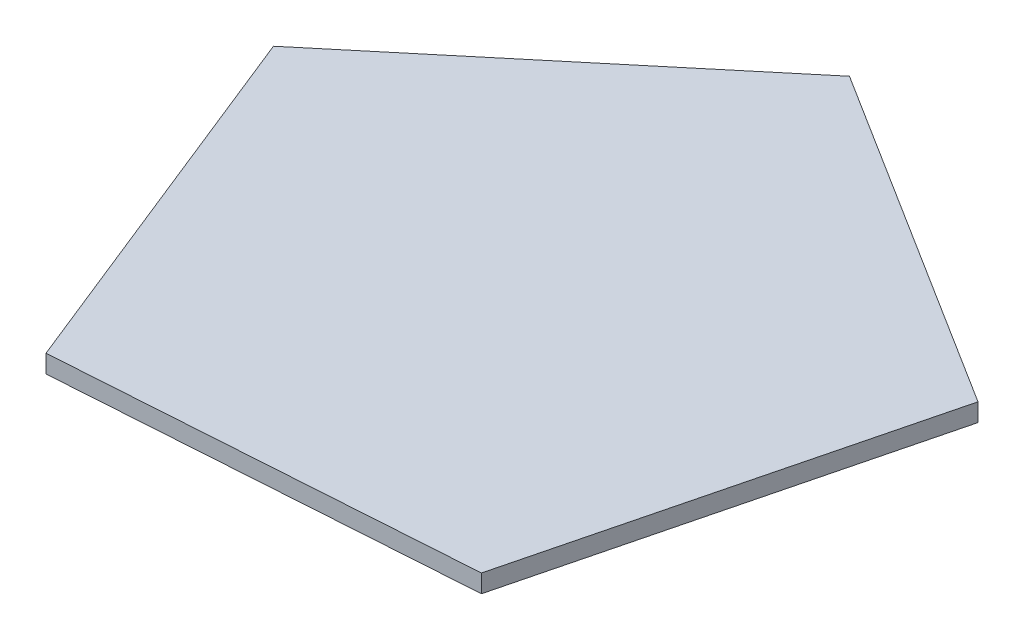
SolidWorks part; units mm, degrees
ref_plane "Front Plane" through (0, 0, 0) normal (0, 0, 1) x (1, 0, 0)
ref_plane "Top Plane" through (0, 0, 0) normal (0, 1, 0) x (1, 0, 0)
ref_plane "Right Plane" through (0, 0, 0) normal (1, 0, 0) x (0, 0, -1)
sketch "Sketch1" plane through (0, 0, 0) normal (0, 1, 0) x (1, 0, 0)
  line L1 (-59.9258, 15.1181) -> (-32.8962, -52.3211)
  line L2 (-32.8962, -52.3211) -> (39.5948, -47.4543)
  line L3 (39.5948, -47.4543) -> (57.3672, 22.9927)
  line L4 (57.3672, 22.9927) -> (-4.14, 61.6646)
  line L5 (-4.14, 61.6646) -> (-59.9258, 15.1181)
  circle A0 centre (0, 0) radius 50 construction
  dimension "D1" = 100
extrude "Boss-Extrude1" add sketch "Sketch1" along normal blind 3.2
sketch "Sketch2" plane through (0, 3.2, 0) normal (0, 1, 0) x (1, 0, 0)
  line L24 (0, 59.0616) -> (10.1589, 52.6744)
  line L25 (0, 59.0616) -> (-1.6926, 56.3695)
  line L26 (10.1589, 52.6744) -> (8.4663, 49.9823)
  line L27 (-1.6926, 56.3695) -> (8.4663, 49.9823)
  line L28 (57.3672, 22.9927) -> (-4.14, 61.6646) construction
  dimension "D1" = 3.18
  dimension "D2" = 12
equation "\"sheetThickness\"= 3.18mm"
equation "\"kerf\"= .22mm"
equation "\"halfkerf\"= \"kerf\" / 2"
equation "\"D1@Sketch2\"=\"sheetThickness\""
equation "\"tabThickness\"=12"
equation "\"D2@Sketch2\"=\"tabThickness\""
